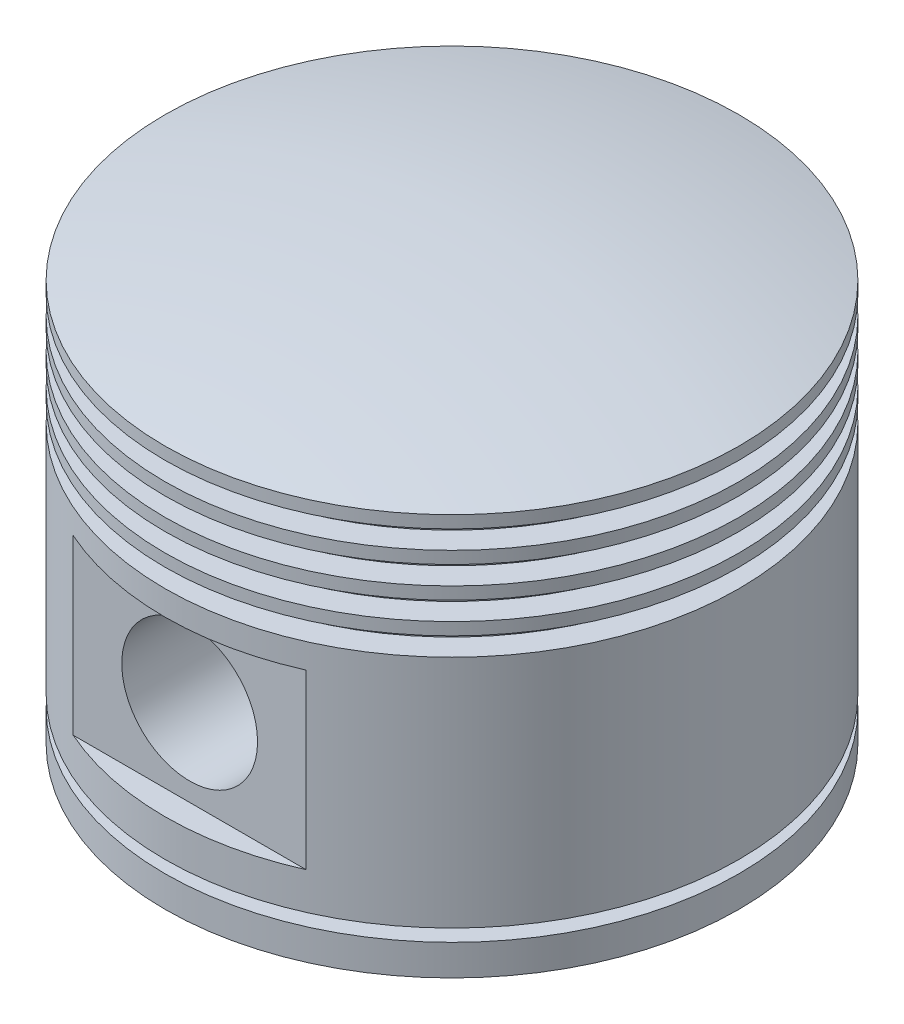
SolidWorks part; units mm, degrees
ref_plane "Front Plane" through (0, 0, 0) normal (0, 0, 1) x (1, 0, 0)
ref_plane "Top Plane" through (0, 0, 0) normal (0, 1, 0) x (1, 0, 0)
ref_plane "Right Plane" through (0, 0, 0) normal (1, 0, 0) x (0, 0, -1)
sketch "Sketch1" plane through (0, 0, 0) normal (0, 0, 1) x (1, 0, 0)
  line L0 (0, 75.5976) -> (0, -76.4896) construction
  line L1 (-46.5, -5.81) -> (-46.5, -7.81)
  line L2 (-46.5, -7.81) -> (-42.5, -7.81)
  line L3 (-42.5, -7.81) -> (-42.5, -10.81)
  line L4 (-42.5, -10.81) -> (-46.5, -10.81)
  line L5 (-46.5, -10.81) -> (-46.5, -12.81)
  line L6 (-46.5, -12.81) -> (-42.5, -12.81)
  line L7 (-42.5, -12.81) -> (-42.5, -15.81)
  line L8 (-42.5, -15.81) -> (-46.5, -15.81)
  line L9 (-46.5, -15.81) -> (-46.5, -17.81)
  line L10 (-46.5, -17.81) -> (-42.5, -17.81)
  line L11 (-42.5, -17.81) -> (-42.5, -20.81)
  line L12 (-42.5, -20.81) -> (-46.5, -20.81)
  line L13 (-46.5, -20.81) -> (-46.5, -22.81)
  line L14 (-46.5, -22.81) -> (-42.5, -22.81)
  line L15 (-42.5, -22.81) -> (-42.5, -25.81)
  line L16 (-42.5, -25.81) -> (-46.5, -25.81)
  line L17 (-46.5, -25.81) -> (-46.5, -63.81)
  line L18 (-46.5, -63.81) -> (-42.5, -63.81)
  line L19 (-42.5, -63.81) -> (-42.5, -65.81)
  line L20 (-42.5, -65.81) -> (-46.5, -65.81)
  line L21 (-46.5, -65.81) -> (-46.5, -70.81)
  line L22 (-46.5, -70.81) -> (-37, -70.81)
  line L23 (-37, -70.81) -> (-37, -8.81)
  line L24 (-37, -8.81) -> (0, -8.81)
  line L25 (0, 0) -> (0, -8.81)
  arc A0 (0, 0) -> (-46.5, -5.81) centre (0.0019, -189) ccw
  dimension "D1" = 189
  dimension "D2" = 46.5
  dimension "D3" = 5.81
  dimension "D4" = 2
  dimension "D5" = 3
  dimension "D6" = 4
  dimension "D7" = 2
  dimension "D8" = 2
  dimension "D9" = 2
  dimension "D10" = 3
  dimension "D11" = 3
  dimension "D12" = 3
  dimension "D13" = 5
  dimension "D14" = 2
  dimension "D15" = 4
  dimension "D16" = 37
  dimension "D17" = 62
  dimension "D18" = 70.81
revolve "Revolve1" add sketch "Sketch1" angle 360 about L0
ref_plane "Plane1" through (0, 0, 25) normal (0, 0, 1) x (1, 0, 0)
sketch "Sketch2" plane through (0, 0, 25) normal (0, 0, 1) x (1, 0, 0)
  line L0 (-46.5, -70.81) -> (46.5, -70.81) construction
  circle A0 centre (0, -43.81) radius 19.5
  dimension "D1" = 39
  dimension "D2" = 27
extrude "Boss-Extrude1" add sketch "Sketch2" along normal up to next
mirror "Mirror1" about plane through (0, 0, 0) normal (0, 0, 1) of "Boss-Extrude1"
sketch "Sketch3" plane through (0, 0, 0) normal (0, 0, 1) x (1, 0, 0)
  line L0 (-46.5, -70.81) -> (46.5, -70.81) construction
  circle A0 centre (0, -43.81) radius 11
  dimension "D1" = 22
  dimension "D2" = 27
extrude "Cut-Extrude1" cut sketch "Sketch3" against normal through all both and the other way through all
sketch "Sketch4" plane through (0, 0, 0) normal (1, 0, 0) x (0, 0, -1)
  line L1 (42.5, -29.81) -> (50.5, -29.81)
  line L2 (42.5, -29.81) -> (42.5, -57.81)
  line L3 (42.5, -57.81) -> (50.5, -57.81)
  line L4 (50.5, -29.81) -> (50.5, -57.81)
  line L5 (42.5, -29.81) -> (50.5, -57.81) construction
  line L6 (42.5, -57.81) -> (50.5, -29.81) construction
  line L8 (-46.5, -70.81) -> (46.5, -70.81) construction
  point P0 (46.5, -43.81)
  dimension "D1" = 27
  dimension "D2" = 28
  dimension "D3" = 8
extrude "Cut-Extrude2" cut sketch "Sketch4" against normal through all both and the other way through all
mirror "Mirror2" about plane through (0, 0, 0) normal (0, 0, 1) of "Cut-Extrude2"
ref_axis "Axis1" through (0, -63.81, 0) along (0, 1, 0)
